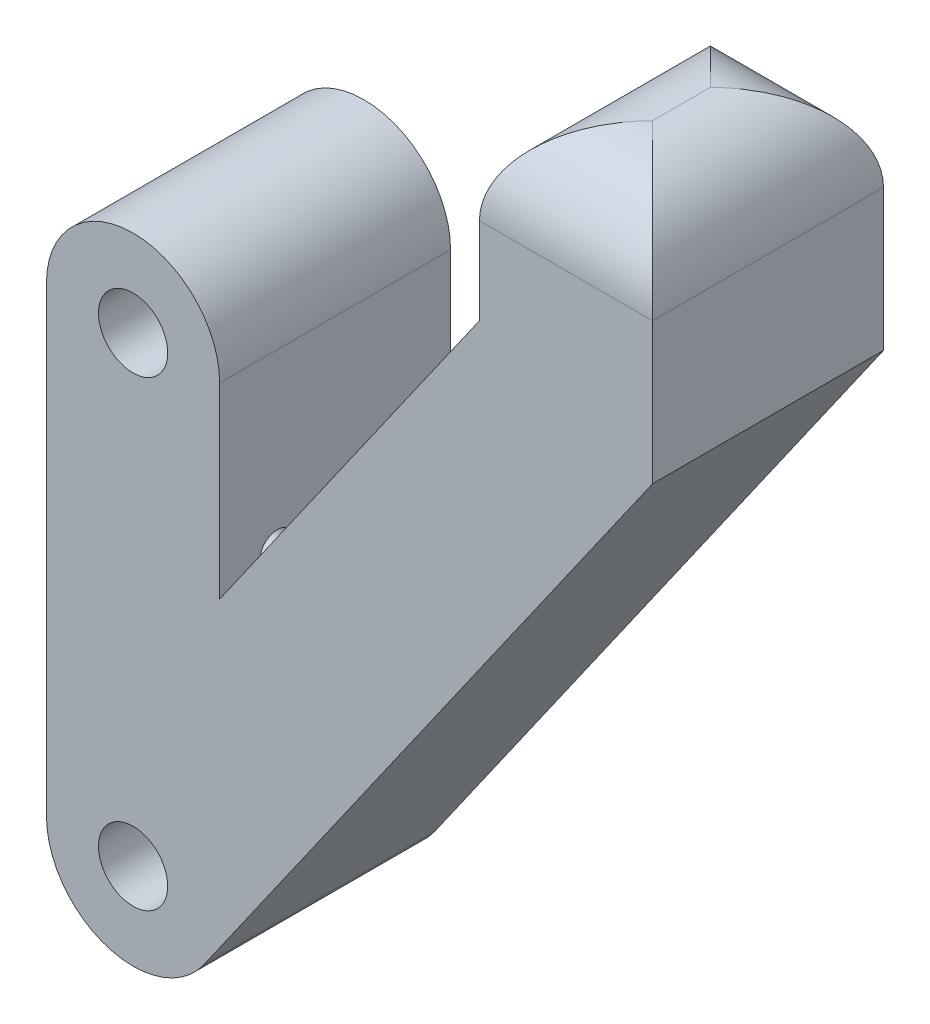
SolidWorks part; units mm, degrees
ref_plane "Front Plane" through (0, 0, 0) normal (0, 0, 1) x (1, 0, 0)
ref_plane "Top Plane" through (0, 0, 0) normal (0, 1, 0) x (1, 0, 0)
ref_plane "Right Plane" through (0, 0, 0) normal (1, 0, 0) x (0, 0, -1)
sketch "Sketch1" plane through (0, 0, 0) normal (0, 0, 1) x (1, 0, 0)
  line L0 (-3.75, 0) -> (-3.75, 20)
  line L2 (3.75, 20) -> (3.75, 11.8935)
  line L3 (3.75, 11.8935) -> (15, 27.9601)
  line L8 (3.75, 11.8935) -> (-3.75, 11.8935) construction
  line L9 (15, 27.9601) -> (21.1436, 23.6583) construction
  line L10 (22.5, 25.5954) -> (22.5, 35.4601)
  line L11 (22.5, 35.4601) -> (15, 35.4601)
  line L12 (15, 35.4601) -> (15, 27.9601)
  line L13 (3.75, 11.8935) -> (9.8936, 7.5917) construction
  line L14 (9.8936, 7.5917) -> (21.1436, 23.6583)
  line L15 (21.1436, 23.6583) -> (22.5, 25.5954)
  line L16 (9.8936, 7.5917) -> (3.0718, -2.1509)
  line L17 (21.1436, 23.6583) -> (22.5, 25.5954)
  circle A3 centre (0, 0) radius 1.5
  circle A5 centre (0, 20) radius 1.5
  arc A6 (-3.75, 0) -> (3.0718, -2.1509) centre (0, 0) ccw
  arc A7 (-3.75, 20) -> (3.75, 20) centre (0, 20) cw
  point P8 (1.9282, -1.5913)
  point P9 (2.5, 7.4185)
  point P10 (28.0542, 34.5961)
  point P13 (23.5718, 42.9711)
  point P18 (15.1321, 25.9083)
  point P19 (2.5, 10.6195)
  point P20 (0, 0)
  point P22 (-2.4764, 0)
  point P23 (10.1777, 30.806)
  point P24 (8.5208, 25.3314)
  point P26 (11.8954, 25.3728)
  dimension "D1" = 3
  dimension "D6" = 7.5
  dimension "D3" = 35
  dimension "D2" = 7.5
  dimension "D4" = 15
  dimension "D5" = 20
extrude "Boss-Extrude1" add sketch "Sketch1" along normal blind 10 contours A5 | L2 L3 L12 L11 L10 L15 L14 L16 A6 L0 A7 | A3
fillet "Fillet1" radius 3.75 4 edges at (22.5, 35.4601, 5) (18.75, 35.4601, 0) (15, 35.4601, 5) (18.75, 35.4601, 10)
sketch "Sketch2" plane through (-3.75, 0, 0) normal (-1, 0, 0) x (0, 0, 1)
  line L0 (5, 20) -> (5, 0) construction
  line L1 (10, 20) -> (0, 20) construction
  line L2 (10, 0) -> (0, 0) construction
  circle A0 centre (7.5, 12.5) radius 0.75
  circle A2 centre (7.5, 7.5) radius 0.75
  circle A3 centre (2.5, 7.5) radius 0.75
  circle A4 centre (2.5, 12.5) radius 0.75
  dimension "D1" = 1.5
  dimension "D2" = 7.5
  dimension "D3" = 2.5
  dimension "D4" = 7.5
extrude "Cut-Extrude1" cut sketch "Sketch2" against normal up to surface (7.5 mm away) contours A3 | A0 | A4 | A2 up to face at (3.75, 15.9467, 5)
